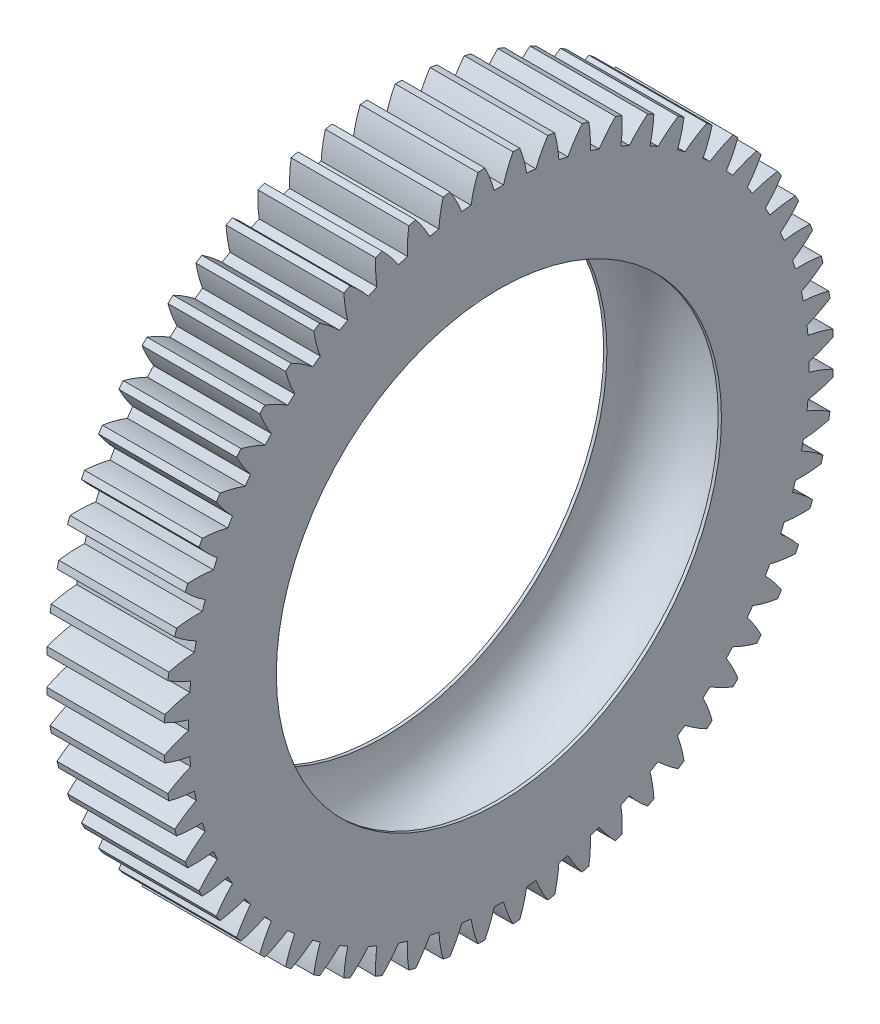
SolidWorks part; units mm, degrees
ref_plane "Plane1" through (0, 0, 0) normal (0, 0, 1) x (1, 0, 0)
ref_plane "Plane2" through (0, 0, 0) normal (0, 1, 0) x (1, 0, 0)
ref_plane "Plane3" through (0, 0, 0) normal (1, 0, 0) x (0, 0, -1)
other "Configuration Table"
sketch "HoldingSke" plane through (0, 0, 0) normal (0, 1, 0) x (1, 0, 0)
  line L0 (0, 0) -> (1, -1.7321)
  line L1 (-15, 0) -> (100, 0) construction
  line L2 (0, 0) -> (-2.1039, 2.3779)
  line L3 (0, 0) -> (-11.863, 4.5341)
  line L4 (0, 0) -> (4.318, 7.479)
  line L5 (0, 0) -> (-46.8476, -17.4728)
  line L6 (0, 0) -> (-5.8027, -3.9151)
  line L7 (-2.1039, 2.3779) -> (8.6586, 51.2059)
  line L8 (-76.2, 54.61) -> (-73.4, 54.61)
  line L9 (-71.009, 38.7566) -> (-53.1078, 45.2721)
  line L10 (-76.2, 71.12) -> (104.1128, 71.12)
  line L11 (0, 0) -> (-7, 0)
  line L12 (-76.2, 101.6) -> (-76.181, 101.6)
  line L13 (24.9733, 27.94) -> (52.9518, 28.4284)
  line L14 (24.9733, 27.94) -> (24.9743, 27.94)
  line L15 (24.9733, 27.94) -> (100.4006, 29.5858)
  line L16 (-63.627, -0.5) -> (-12.827, -0.5)
  circle A0 centre (0, 0) radius 10
  circle A1 centre (0, 0) radius 14.374
  circle A2 centre (0, 0) radius 37.5
  circle A3 centre (0, 0) radius 10
  dimension "Num_teeth" = 60
  dimension "Pitch_radius" = 180.3128
  dimension "Width" = 7
  dimension "Thickness" = 7
sketch "BasProSke" plane through (0, 0, 0) normal (0, 1, 0) x (1, 0, 0)
  line L0 (-10, 0) -> (60, 0) construction
  line L1 (0, 0) -> (0, 15.5)
  line L2 (0, 0) -> (7, 0)
  line L3 (7, 0) -> (7, 15.5)
  line L4 (7, 15.5) -> (0, 15.5)
  dimension "Thickness" = 7
  dimension "Diameter" = 31
revolve "Base-Revolve" add sketch "BasProSke" angle 360 about L0
sketch "TooCutSke" plane through (0, 0, 0) normal (1, 0, 0) x (0, 0, -1)
  line L1 (0, 0) -> (0, 107) construction
  line L2 (0, 0) -> (-0.4259, 14.994) construction
  line L3 (0, 0) -> (-1.5696, 29.9503) construction
  line L4 (-0.4259, 14.994) -> (-0.7848, 14.9751) construction
  arc A0 (0.2149, 14.3724) -> (-0.2149, 14.3724) centre (0, 0) ccw
  arc A1 (0.6627, 15.5112) -> (-0.6627, 15.5112) centre (0, 0) ccw
  circle A2 centre (0, 0) radius 15 construction
  circle A3 centre (0, 0) radius 14.0954 construction
  arc A4 (-0.2149, 14.3724) -> (-0.6627, 15.5112) centre (-5.9936, 12.7576) ccw
  arc A5 (0.6627, 15.5112) -> (0.2149, 14.3724) centre (5.9936, 12.7576) ccw
extrude "ToothCut" cut sketch "TooCutSke" along normal through all
fillet "Breaks" [suppressed] radius 0.01 tangent propagation no
fillet "RootFillets" [suppressed] radius 0.126
pattern_circular "TeethCuts" count 60 every 6 about axis through (-10, 0, 0) along (1, 0, 0) of "ToothCut", "RootFillets", "Breaks"
sketch "HubNeaOneSke" plane through (0, 0, 0) normal (-1, 0, 0) x (0, 0, 1)
  circle A0 centre (0, 0) radius 14.374
  dimension "Diameter" = 28.748
extrude "HubNearOne" [suppressed] add sketch "HubNeaOneSke" along normal blind 43.0001
sketch "HubNeaBotSke" plane through (0, 0, 0) normal (-1, 0, 0) x (0, 0, 1)
  circle A0 centre (0, 0) radius 14.374
  dimension "Diameter" = 28.748
extrude "HubNearBoth" [suppressed] add sketch "HubNeaBotSke" along normal blind 21.5
ref_plane "FarPln" through (7, 0, 0) normal (1, 0, 0) x (0, 0, -1)
sketch "HubFarSke" plane through (7, 0, 0) normal (1, 0, 0) x (0, 0, -1)
  circle A0 centre (0, 0) radius 14.374
  dimension "Diameter" = 28.748
extrude "HubFar" [suppressed] add sketch "HubFarSke" along normal blind 21.5
sketch "BorSke" plane through (0, 0, 0) normal (1, 0, 0) x (0, 0, -1)
  circle A0 centre (0, 0) radius 10
  dimension "Diameter" = 20
extrude "Bore" cut sketch "BorSke" along normal mid plane 100.0001
sketch "KeySke" plane through (0, 0, 0) normal (1, 0, 0) x (0, 0, -1)
  line L0 (-3, 0) -> (-3, 12.8)
  line L1 (-3, 12.8) -> (3, 12.8)
  line L2 (3, 12.8) -> (3, 0)
  line L3 (0, 0) -> (0, 34) construction
  line L4 (-3, 0) -> (3, 0)
  dimension "Width" = 6
extrude "Keyway" [suppressed] cut sketch "KeySke" along normal mid plane 100.0001
pattern_circular "Keyway2" [suppressed] count 2 every 90 about axis through (-10, 0, 0) along (1, 0, 0) reverse direction yes
scale "Scale1" bodies to scale 103 scale about centroid uniform scaling yes scale factor 0.97
sketch "Sketch1" plane through (6.895, 0, 0) normal (1, 0, 0) x (0, 0, -1)
  circle A0 centre (0, 0) radius 10
  dimension "D1" = 20
extrude "Cut-Extrude1" cut sketch "Sketch1" along normal blind 3 and the other way blind 31
ref_axis "Axis1" through (0.105, 0, 0) along (1, 0, 0)
ref_plane "Plane5" through (3.5, 0, 0) normal (1, 0, 0) x (0, 0, -1)
sketch "Sketch11" plane through (3.5, 0, 0) normal (1, 0, 0) x (0, 0, -1)
  circle A0 centre (0, 0) radius 10
  circle A1 centre (0, 0) radius 10 construction
sweep "Cut-Sweep2" cut path "Sketch11" circular profile diameter 5 parameters "D3"=5
sketch "Sketch19" plane through (6.895, 0, 0) normal (1, 0, 0) x (0, 0, -1)
  circle A0 centre (0, 0) radius 21.106
extrude "Cut-Extrude2" cut sketch "Sketch19" against normal blind 0.75
sketch "Sketch21" plane through (0.105, 0, 0) normal (-1, 0, 0) x (0, 0, 1)
  circle A0 centre (0, 0) radius 17.7632
extrude "Cut-Extrude3" cut sketch "Sketch21" against normal blind 0.75
equation "' \"Module@HoldingSke\" = 6.35"
equation "' \"Num_teeth@HoldingSke\" = 12"
equation "' \"Ap@HoldingSke\" =  20"
equation "' \"Ap@HoldingSke\" = 20"
equation "' \"Width@HoldingSke\" = 0.5 * 25.4"
equation "' \"Hub_dia@HoldingSke\"= 1 * 25.4"
equation "' \"Hub_dia@HoldingSke\" = 1 * 25.4"
equation "' \"Overall_len@HoldingSke\" = 1.0 * 25.4"
equation "' \"Bore@HoldingSke\" = 0.75 * 25.4"
equation "' \"T_dim@HoldingSke\" = 0.1 * 25.4"
equation "' \"Width@KeySke\" = 0.25 * 25.4"
equation "' \"Show_teeth@HoldingSke\" = 13"
equation "' \"Backlash@HoldingSke\" = 0.009 * 25.4"
equation "' \"Addendum_fac@HoldingSke\" = 1.0"
equation "' \"Dedendum_fac@HoldingSke\" = 1.25"
equation "' \"Dedendum_add@HoldingSke\" = 0.00005 * 25.4"
equation "' \"Clearance_fac@HoldingSke\" = 0.25"
equation "\"Pitch@HoldingSke\" = 1 / \"Module@HoldingSke\""
equation "\"Overcut_dia@TooCutSke\" = (\"Num_teeth@HoldingSke\" + 2 * \"Addendum_fac@HoldingSke\") / \"Pitch@HoldingSke\" + 0.002 * 25.4"
equation "\"Pitch_dia@TooCutSke\" = \"Num_teeth@HoldingSke\" / \"Pitch@HoldingSke\""
equation "\"Base_dia@TooCutSke\" = \"Num_teeth@HoldingSke\" / \"Pitch@HoldingSke\" * cos((\"Ap@HoldingSke\"  * 3.14159265 / 180))"
equation "\"Root_dia@TooCutSke\" = (\"Num_teeth@HoldingSke\" + 2) / \"Pitch@HoldingSke\" - 2 * (\"Addendum_fac@HoldingSke\" + \"Dedendum_fac@HoldingSke\") / \"Pitch@HoldingSke\" - \"Dedendum_add@HoldingSke\" * 2"
equation "\"Half_ang@TooCutSke\" = 180 / \"Num_teeth@HoldingSke\""
equation "\"Half_CT@TooCutSke\" = \"Num_teeth@HoldingSke\" / \"Pitch@HoldingSke\" * sin((3.14159265 / 2 / \"Num_teeth@HoldingSke\")) / 2 - 7 * \"Backlash@HoldingSke\" / 4"
equation "\"Flank_rad@TooCutSke\" = \"Num_teeth@HoldingSke\" / \"Pitch@HoldingSke\" / 5"
equation "\"Radius@RootFillets\" = \"Clearance_fac@HoldingSke\" / \"Pitch@HoldingSke\" + \"Dedendum_add@HoldingSke\""
equation "\"Break_rad@Breaks\" = 0.02 / \"Pitch@HoldingSke\""
equation "\"Thickness@HoldingSke\" = \"Width@HoldingSke\""
equation "\"OAL@HoldingSke\" = \"Thickness@HoldingSke\""
equation "\"MHD@HoldingSke\" = (\"Num_teeth@HoldingSke\" + 2) / \"Pitch@HoldingSke\" - 2 * (\"Addendum_fac@HoldingSke\" + \"Dedendum_fac@HoldingSke\")  / \"Pitch@HoldingSke\" - \"Dedendum_add@HoldingSke\" * 2"
equation "\"MBD@HoldingSke\" = (\"Num_teeth@HoldingSke\" + 2) / \"Pitch@HoldingSke\" - 2 * (\"Addendum_fac@HoldingSke\" + \"Dedendum_fac@HoldingSke\")  / \"Pitch@HoldingSke\" - \"Dedendum_add@HoldingSke\" * 2 - 0.002 * 25.4"
equation "\"MHD@HoldingSke\" = ((sgn( \"MHD@HoldingSke\" - \"Hub_dia@HoldingSke\" )-1)*( \"MHD@HoldingSke\" - \"Hub_dia@HoldingSke\" ))/-2+ \"Hub_dia@HoldingSke\""
equation "\"MBD@HoldingSke\" = ((sgn( \"MBD@HoldingSke\" - \"Bore@HoldingSke\" )-1)*( \"MBD@HoldingSke\" - \"Bore@HoldingSke\" ))/-2+ \"Bore@HoldingSke\""
equation "\"OAL@HoldingSke\" = ((sgn( \"OAL@HoldingSke\" - \"Overall_len@HoldingSke\" )+1)*( \"OAL@HoldingSke\" - \"Overall_len@HoldingSke\" ))/2 + \"Overall_len@HoldingSke\" + 0.000002 * 25.4"
equation "\"Num_teeth@TeethCuts\" = int( \"Show_teeth@HoldingSke\" ) + 1"
equation "\"Num_teeth@TeethCuts\" = ((sgn( \"Num_teeth@TeethCuts\" - \"Num_teeth@HoldingSke\" )-1)*( \"Num_teeth@TeethCuts\" - \"Num_teeth@HoldingSke\" ))/-2+ \"Num_teeth@HoldingSke\""
equation "\"Num_teeth@TeethCuts\" = ((sgn( \"Num_teeth@TeethCuts\" - 2.0)+1)*( \"Num_teeth@TeethCuts\" - 2.0))/2 +2.0"
equation "\"Angle@TeethCuts\" = 360.0 / \"Num_teeth@HoldingSke\""
equation "\"Diameter@BasProSke\" = (\"Num_teeth@HoldingSke\" + 2 * \"Addendum_fac@HoldingSke\") / \"Pitch@HoldingSke\""
equation "\"Thickness@BasProSke\"  = \"Thickness@HoldingSke\""
equation "' \"Fillet_rad@BasProSke\" =  \"Thickness@HoldingSke\" * 0.05"
equation "' \"Fillet_rad@BasProSke\" = \"Thickness@HoldingSke\" * 0.05"
equation "\"MHD@HoldingSke\" = ((sgn( \"MHD@HoldingSke\" - \"Root_dia@TooCutSke\" )-1)*( \"MHD@HoldingSke\" - \"Root_dia@TooCutSke\" ))/-2+ \"Root_dia@TooCutSke\""
equation "\"Diameter@HubNeaOneSke\" = \"MHD@HoldingSke\""
equation "\"Length@HubNearOne\" = \"OAL@HoldingSke\" - \"Thickness@BasProSke\""
equation "\"Diameter@HubNeaBotSke\" = \"MHD@HoldingSke\""
equation "\"Length@HubNearBoth\" = ( \"OAL@HoldingSke\" - \"Thickness@BasProSke\" ) / 2.0"
equation "\"Thickness@FarPln\" = \"Thickness@BasProSke\""
equation "\"Diameter@HubFarSke\" = \"MHD@HoldingSke\""
equation "\"Length@HubFar\" = ( \"OAL@HoldingSke\" - \"Thickness@BasProSke\" ) / 2.0"
equation "\"Diameter@BorSke\" = \"MBD@HoldingSke\""
equation "\"D1@Bore\" = \"OAL@HoldingSke\" * 2.0"
equation "\"D1@Keyway\" = \"OAL@HoldingSke\" * 2.0"
equation "\"Offset@KeySke\" = \"T_dim@HoldingSke\" + \"MBD@HoldingSke\" / 2.0"
